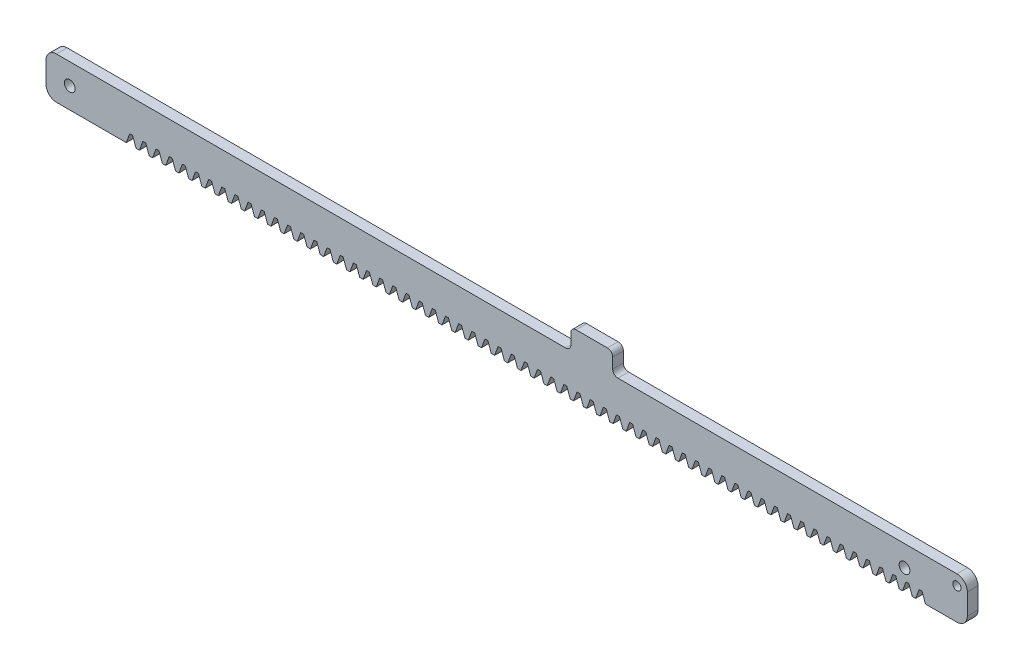
SolidWorks part; units mm, degrees
material "PC High Viscosity"
ref_plane "Front Plane" through (0, 0, 0) normal (0, 0, 1) x (1, 0, 0)
ref_plane "Top Plane" through (0, 0, 0) normal (0, 1, 0) x (1, 0, 0)
ref_plane "Right Plane" through (0, 0, 0) normal (1, 0, 0) x (0, 0, -1)
sketch "Sketch1" plane through (0, 0, 0) normal (0, 0, 1) x (1, 0, 0)
  line L1 (0, 0) -> (40.5307, 0)
  line L2 (0, 0) -> (0, 25.4)
  line L3 (0, 25.4) -> (40.5308, 25.4)
  line L4 (558.8, 0) -> (558.8, 25.4)
  line L7 (533.4, 25.4) -> (558.8, 25.4)
  line L8 (40.5308, 25.4) -> (318.3103, 25.4)
  line L9 (40.5307, 0) -> (558.8, 0)
  line L11 (558.8, 22.7162) -> (552.45, 26.3823) construction
  line L12 (552.45, 26.3823) -> (546.1, 22.7162) construction
  line L13 (546.1, 22.7162) -> (546.1, 15.3838) construction
  line L14 (546.1, 15.3838) -> (552.45, 11.7177) construction
  line L15 (552.45, 11.7177) -> (558.8, 15.3838) construction
  line L16 (558.8, 15.3838) -> (558.8, 22.7162) construction
  line L19 (590.55, 0) -> (590.55, 10.0162) construction
  line L20 (590.55, 10.0162) -> (76.2, 10.0162) construction
  line L21 (76.2, 10.0162) -> (76.2, 0) construction
  line L22 (447.3033, 25.4) -> (533.4, 25.4)
  line L32 (318.3103, 25.4) -> (318.3103, 38.1)
  line L33 (318.3103, 38.1) -> (343.7103, 38.1)
  line L34 (343.7103, 38.1) -> (343.7103, 25.4)
  line L35 (343.7103, 25.4) -> (447.3033, 25.4)
  circle A0 centre (552.45, 19.05) radius 2.4892
  circle A1 centre (552.45, 19.05) radius 6.35 construction
  dimension "D5" = 4.9784
  dimension "D6" = 318.3103
  dimension "D7" = 12.7
  dimension "D1" = 558.8
  dimension "D2" = 25.4
  dimension "D3" = 25.4
  dimension "D4" = 12.7
extrude "Boss-Extrude1" add sketch "Sketch1" along normal blind 6.477 contours L3 | L1 L4 L3 L2 A0 | L1 region at (280.1818, 13.1154, 0)
fillet "Fillet2" radius 6.35 4 edges at (558.8, 0, 3.2385) (0, 0, 3.2385) (0, 25.4, 3.2385) (558.8, 25.4, 3.2385)
sketch "Sketch2" plane through (0, 0, 6.477) normal (0, 0, 1) x (1, 0, 0)
  line L0 (533.4, 0) -> (44.45, 0)
  line L1 (44.45, 0) -> (44.45, 5.715)
  line L2 (44.45, 5.715) -> (533.4, 5.715)
  line L3 (533.4, 5.715) -> (533.4, 0)
  line L5 (532.4755, 2.54) -> (524.311, 2.54) construction
  line L6 (533.4, 0) -> (531.3199, 5.715)
  line L8 (527.4688, 0) -> (533.4, 0)
  line L10 (531.3199, 5.715) -> (529.5488, 5.715)
  line L11 (533.4, 0) -> (527.4688, 0)
  line L12 (527.4688, 0) -> (529.5488, 5.715)
  line L13 (529.5488, 5.715) -> (531.3199, 5.715)
  line L14 (533.4, 0) -> (527.4688, 0)
  line L15 (529.5488, 5.715) -> (531.3199, 5.715)
  line L16 (533.4, 0) -> (527.4688, 0)
  line L17 (527.4688, 0) -> (533.4, 0)
  line L19 (531.3199, 5.715) -> (529.5488, 5.715) construction
  line L20 (527.4688, 0) -> (533.4, 0) construction
  line L22 (558.8, 0) -> (558.8, 25.4) construction
  line L23 (40.5307, 0) -> (558.8, 0) construction
  line L24 (0, 6.35) -> (0, 19.05) construction
  point P2 (0, 0)
  point P8 (528.3932, 2.54)
  point P16 (532.4755, 2.54)
  dimension "D1" = 70
  dimension "D2" = 2.54
  dimension "D3" = 3.175
  dimension "D4" = 70
  dimension "D5" = 1.7711
  dimension "D6" = 25.4
  dimension "D7" = 44.45
extrude "Cut-Extrude1" cut sketch "Sketch2" against normal through all contours L12 L0 L8 L6 L2 region at (530.4344, 2.343, 6.477)
pattern_linear "LPattern1" count 61 spacing 7.9796 along (-1, 0, 0) of "Cut-Extrude1"
sketch "Sketch3" plane through (0, 0, 6.477) normal (0, 0, 1) x (1, 0, 0)
  line L0 (6.35, 0) -> (48.69, 0) construction
  line L2 (533.4, 25.4) -> (558.8, 25.4) construction
  line L3 (558.8, 0) -> (558.8, 25.4) construction
  line L4 (0, 6.35) -> (0, 19.05) construction
  circle A0 centre (520.7, 12.7) radius 3.2639
  circle A2 centre (14.3939, 12.7) radius 3.2639
  point P12 (0, 16.7159)
  dimension "D2" = 6.5278
  dimension "D1" = 12.7
  dimension "D3" = 38.1
  dimension "D6" = 6.5278
  dimension "D4" = 12.7
  dimension "D5" = 14.3939
extrude "Cut-Extrude2" cut sketch "Sketch3" against normal through all
fillet "Fillet3" radius 3.175 4 edges at (318.3103, 38.1, 3.2385) (318.3103, 25.4, 3.2385) (343.7103, 38.1, 3.2385) (343.7103, 25.4, 3.2385)
